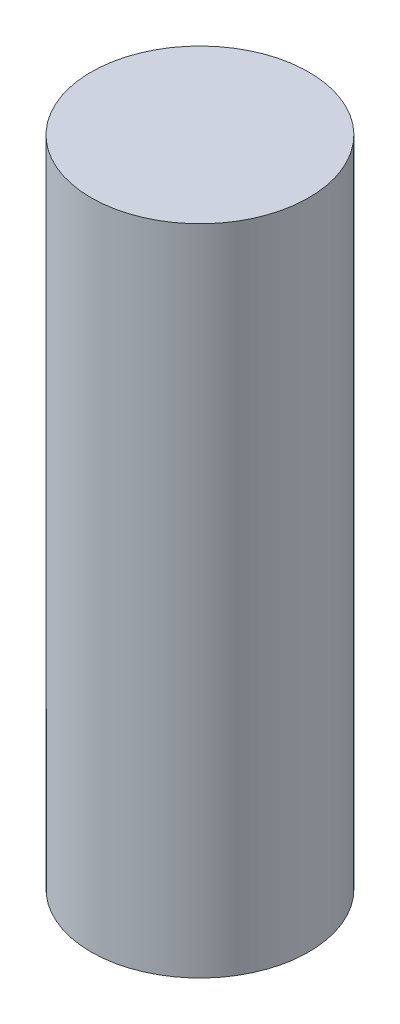
SolidWorks part; units mm, degrees
ref_plane "Front" through (0, 0, 0) normal (0, 0, 1) x (1, 0, 0)
ref_plane "Top" through (0, 0, 0) normal (0, 1, 0) x (1, 0, 0)
ref_plane "Right" through (0, 0, 0) normal (1, 0, 0) x (0, 0, -1)
sketch "Sketch1" plane through (0, 0, 0) normal (0, 1, 0) x (1, 0, 0)
  circle A0 centre (0, 0) radius 4.7625
  circle A1 centre (0, 0) radius 6.35
  dimension "D1" = 9.525
  dimension "D2" = 12.7
extrude "Boss-Extrude1" add sketch "Sketch1" along normal blind 25.4 contours A1
extrude "Boss-Extrude2" add sketch "Sketch1<4>" against normal blind 12.7
sketch "Sketch1<4>" plane through (0, 0, 0) normal (0, 1, 0) x (1, 0, 0) same geometry as "Sketch1"
